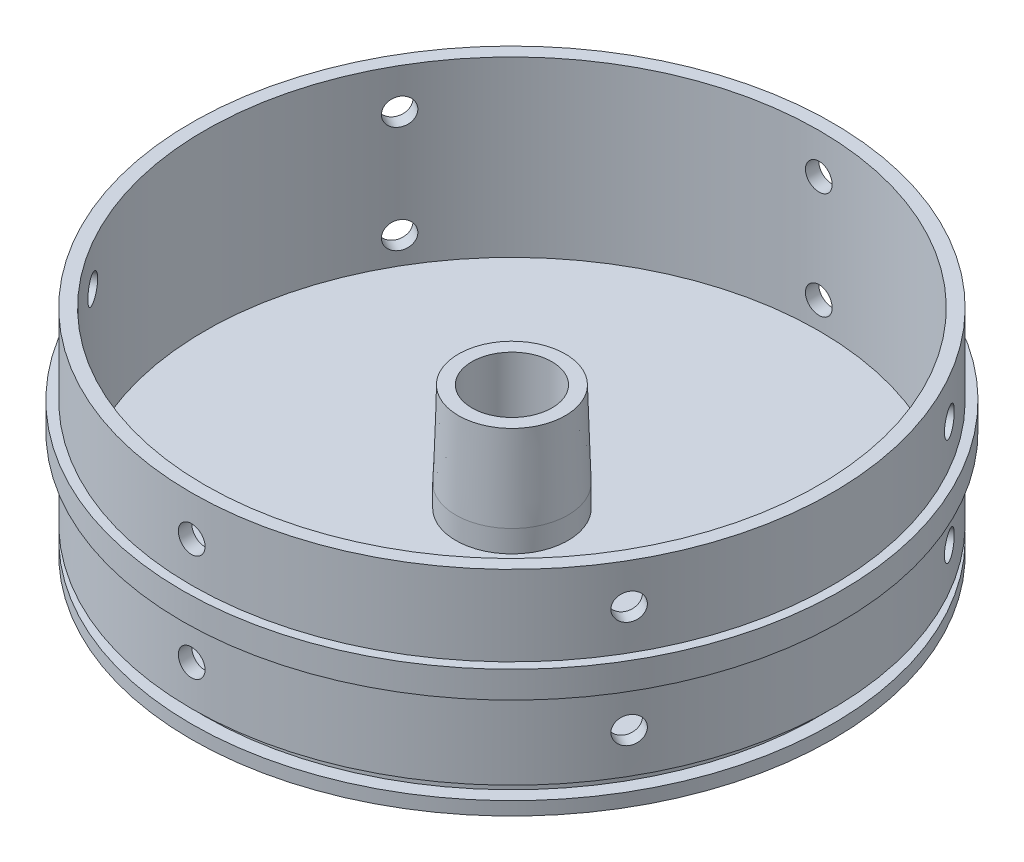
SolidWorks part; units mm, degrees
material "2024-T4"
ref_plane "Front Plane" through (0, 0, 0) normal (0, 0, 1) x (1, 0, 0)
ref_plane "Top Plane" through (0, 0, 0) normal (0, 1, 0) x (1, 0, 0)
ref_plane "Right Plane" through (0, 0, 0) normal (1, 0, 0) x (0, 0, -1)
sketch "Sketch1" plane through (0, 0, 0) normal (0, 1, 0) x (1, 0, 0)
  circle A0 centre (0, 0) radius 78.359
  circle A2 centre (0, 0) radius 76.2
  circle A3 centre (0, 0) radius 73.025
  dimension "D1" = 156.718
  dimension "D2" = 152.4
  dimension "D3" = 3.175
extrude "Boss-Extrude1" add sketch "Sketch1" along normal blind 6.35 contours A0 A2 region at (-78.1374, 0, 0)
extrude "Boss-Extrude2" add sketch "Sketch1<3>" along normal blind 25.4 contours A2 A3 region at (-74.0447, 0, 0)
sketch "Sketch1<3>" plane through (0, 0, 0) normal (0, 1, 0) x (1, 0, 0) same geometry as "Sketch1"
sketch "Sketch2" plane through (0, 0, 0) normal (0, -1, 0) x (1, 0, 0)
  circle A0 centre (0, 0) radius 73.025 construction
  circle A1 centre (0, 0) radius 73.025
  circle A2 centre (0, 0) radius 76.2
  dimension "D1" = 3.175
extrude "Boss-Extrude3" add sketch "Sketch2" along normal blind 25.4
sketch "Sketch3" plane through (0, -25.4, 0) normal (0, -1, 0) x (1, 0, 0)
  circle A1 centre (0, 0) radius 76.2
  circle A2 centre (0, 0) radius 76.2
  dimension "D1" = 0
extrude "Boss-Extrude4" add sketch "Sketch3" against normal blind 9.525
sketch "Sketch5" plane through (0, 0, 0) normal (0, 0, 1) x (1, 0, 0)
  line L0 (-76.2, -25.4) -> (76.2, -25.4) construction
  line L1 (-76.2, 0) -> (-76.2, -25.4) construction
  line L2 (-76.2, -25.4) -> (76.2, -25.4)
  line L3 (-76.2, 0) -> (-76.2, -25.4)
  line L4 (-76.2, -22.225) -> (-73.025, -22.225)
  line L5 (-73.025, -22.225) -> (-73.025, -19.05)
  line L6 (-73.025, -19.05) -> (-76.2, -19.05)
  line L7 (0, 0) -> (0, -25.4) construction
  dimension "D1" = 3.175
  dimension "D2" = 3.175
  dimension "D3" = 3.175
revolve "Cut-Revolve1" cut sketch "Sketch5" angle 360 about L7 region at (-74.6125, -20.6375, 0)
ref_plane "Plane1" through (0, 0, 76.2) normal (0, 0, 1) x (1, 0, 0)
sketch "Sketch6" plane through (0, 0, 76.2) normal (0, 0, 1) x (1, 0, 0)
  line L0 (78.359, 6.35) -> (-78.359, 6.35) construction
  line L1 (78.359, 6.35) -> (-78.359, 6.35)
  line L2 (-76.2, 0) -> (76.2, 0) construction
  line L3 (-76.2, 0) -> (76.2, 0)
  circle A0 centre (0, 15.875) radius 3.175
  circle A1 centre (0, -9.525) radius 3.175
  dimension "D3" = 6.35
  dimension "D4" = 6.35
  dimension "D1" = 9.525
  dimension "D2" = 9.525
extrude "Cut-Extrude1" cut sketch "Sketch6" against normal blind 12.7 contours A0 | A1 region at (0, 15.875, 76.2) region at (0, -9.525, 76.2)
pattern_circular "CirPattern1" count 6 over 360 about axis through (0, 25.4, 0) along (0, -1, 0) of "Cut-Extrude1"
sketch "Sketch7" plane through (0, -15.875, 0) normal (0, 1, 0) x (1, 0, 0)
  circle A0 centre (0, 0) radius 9.525
  circle A1 centre (0, 0) radius 13.335
  dimension "D1" = 19.05
  dimension "D2" = 26.67
extrude "Boss-Extrude5" add sketch "Sketch7" along normal blind 25.4
extrude "Cut-Extrude2" cut sketch "Sketch7<3>" against normal through all contours A0
sketch "Sketch7<3>" plane through (0, -15.875, 0) normal (0, 1, 0) x (1, 0, 0) same geometry as "Sketch7"
chamfer "Chamfer1" distance 20.16 angle 1.79 1 edges at (0, 9.525, 13.335) first distance on face at (0, 9.525, 13.335)
